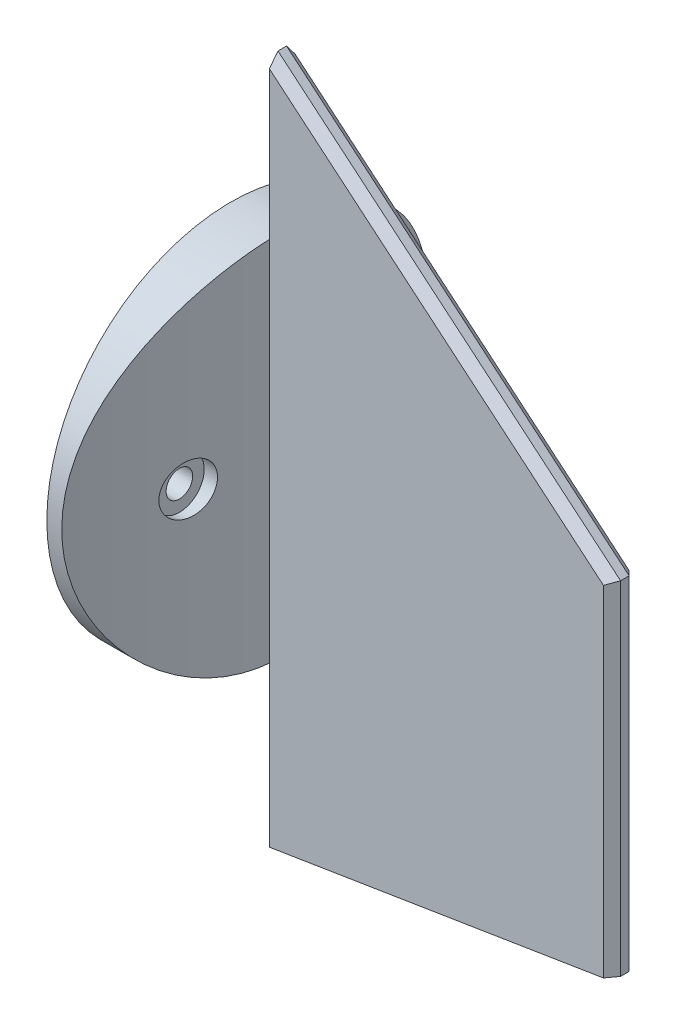
SolidWorks part; units mm, degrees
ref_plane "Front Plane" through (0, 0, 0) normal (0, 0, 1) x (1, 0, 0)
ref_plane "Top Plane" through (0, 0, 0) normal (0, 1, 0) x (1, 0, 0)
ref_plane "Right Plane" through (0, 0, 0) normal (1, 0, 0) x (0, 0, -1)
sketch "Sketch13" plane through (0, 0, 0) normal (1, 0, 0) x (0, 0, -1)
  line L0 (-2.6217, -2.2425) -> (-1.8172, -14.1833)
  line L1 (2.1766, -14.1326) -> (2.6778, -2.1753)
  arc A0 (2.6778, -2.1753) -> (-2.6217, -2.2425) centre (0, 0) ccw
  arc A1 (-1.8172, -14.1833) -> (2.1766, -14.1326) centre (0.1783, -14.0489) ccw
  circle A2 centre (0, 0) radius 16.3675
  dimension "D1" = 3.45
  dimension "D2" = 2
  dimension "D6" = 32.735
  dimension "D3" = 0.1783
  dimension "D4" = 2.1766
  dimension "D5" = 2.6778
extrude "Boss-Extrude11" add sketch "Sketch13" along normal mid plane 1.524
sketch "Sketch14" plane through (0.762, 0, 0) normal (1, 0, 0) x (0, 0, -1)
  circle A0 centre (0, 0) radius 16.3675
  circle A1 centre (0, 0) radius 16.3675 construction
extrude "Boss-Extrude12" add sketch "Sketch14" along normal mid plane 1.016
sketch "Sketch15" plane through (0, 0, 0) normal (0, 0, 1) x (1, 0, 0)
  line L0 (1.27, 18.3324) -> (1.27, -21.3321) construction
  line L1 (1.27, 0) -> (1.27, 25.4)
  line L2 (1.27, -16.3675) -> (1.27, 16.3675) construction
  line L3 (1.27, 0) -> (1.27, -25.4)
  line L4 (1.27, -25.4) -> (26.67, -21.3131)
  line L5 (26.67, -21.3131) -> (26.67, 4.0869)
  line L6 (26.67, 4.0869) -> (1.27, 25.4)
  dimension "D1" = 50
  dimension "D2" = 25.4
  dimension "D3" = 25.4
  dimension "D4" = 25.4
  dimension "D5" = 25.4
extrude "Boss-Extrude13" add sketch "Sketch15" along normal mid plane 1.905
fillet "Chamfer6" radius 0.762 4 edges at (13.97, 14.7434, -0.9525) (26.67, -8.6131, -0.9525) (26.67, -8.6131, 0.9525) (13.97, 14.7434, 0.9525) profile chamfer
sketch "Sketch20" plane through (-0.762, 0, 0) normal (-1, 0, 0) x (0, 0, 1)
  line L2 (1.8172, -14.1833) -> (2.6217, -2.2425)
  line L3 (-2.6778, -2.1753) -> (-2.1766, -14.1326)
  line L4 (1.8172, -14.1833) -> (2.6217, -2.2425)
  line L5 (-2.6778, -2.1753) -> (-2.1766, -14.1326)
  circle A1 centre (0, 0) radius 16.3675
  circle A2 centre (0, 0) radius 16.3675
  arc A4 (2.6217, -2.2425) -> (-2.6778, -2.1753) centre (0, 0) ccw
  arc A5 (-2.1766, -14.1326) -> (1.8172, -14.1833) centre (-0.1783, -14.0489) ccw
  arc A6 (2.6217, -2.2425) -> (-2.6778, -2.1753) centre (0, 0) ccw
  arc A7 (-2.1766, -14.1326) -> (1.8172, -14.1833) centre (-0.1783, -14.0489) ccw
  dimension "D1" = 0
  dimension "D2" = 0
sketch "Sketch26" plane through (0.254, 0, 0) normal (-1, 0, 0) x (0, 0, 1)
  line L2 (-2.6778, -2.1753) -> (-2.1766, -14.1326)
  line L3 (1.8172, -14.1833) -> (2.6217, -2.2425)
  line L4 (-2.6778, -2.1753) -> (-2.1766, -14.1326)
  line L5 (1.8172, -14.1833) -> (2.6217, -2.2425)
  arc A2 (2.6217, -2.2425) -> (-2.6778, -2.1753) centre (0, 0) ccw
  arc A3 (-2.1766, -14.1326) -> (1.8172, -14.1833) centre (-0.1783, -14.0489) ccw
  arc A4 (2.6217, -2.2425) -> (-2.6778, -2.1753) centre (0, 0) ccw
  arc A5 (-2.1766, -14.1326) -> (1.8172, -14.1833) centre (-0.1783, -14.0489) ccw
  dimension "D1" = 0
extrude "Boss-Extrude19" add sketch "Sketch26" along normal up to surface (1.016 mm away) up to face at (-0.762, 0, -16.3675)
sketch "Sketch27" plane through (1.27, 0, 0) normal (1, 0, 0) x (0, 0, -1)
  line L1 (0.9525, 16.3398) -> (0.9525, -16.3398)
  line L3 (0.9525, 16.3398) -> (0.9525, -16.3398)
  line L5 (-0.9525, -16.3398) -> (-0.9525, 16.3398)
  line L6 (-0.9525, -16.3398) -> (-0.9525, 16.3398)
  arc A1 (0.9525, -16.3398) -> (0.9525, 16.3398) centre (0, 0) ccw
  arc A2 (0.9525, -16.3398) -> (0.9525, 16.3398) centre (0, 0) ccw
  arc A3 (-0.9525, 16.3398) -> (-0.9525, -16.3398) centre (0, 0) ccw
  arc A4 (-0.9525, 16.3398) -> (-0.9525, -16.3398) centre (0, 0) ccw
  dimension "D1" = 0
  dimension "D2" = 0
extrude "Boss-Extrude20" add sketch "Sketch27" along normal blind 1.524
sketch "Sketch28" plane through (2.794, 0, 0) normal (1, 0, 0) x (0, 0, -1)
  line L0 (-23.2899, 0) -> (37.7845, 0) construction
  line L1 (-16.3675, 18.2766) -> (-16.3675, 10.7478) construction
  line L2 (0, 0) -> (0, -28.4596) construction
  circle A0 centre (-7.6248, 0) radius 2.2098
  arc A1 (-0.9525, 16.3398) -> (-0.9525, -16.3398) centre (0, 0) ccw construction
  circle A2 centre (7.6248, 0) radius 2.2098
  dimension "D1" = 4.4196
  dimension "D2" = 8.7427
extrude "Cut-Extrude9" cut sketch "Sketch28" against normal blind 1.524
sketch "Sketch29" plane through (1.27, 0, 0) normal (1, 0, 0) x (0, 0, -1)
  circle A0 centre (-7.6248, 0) radius 1.1811
  circle A1 centre (7.6248, 0) radius 1.1811
  dimension "D1" = 2.3622
  dimension "D2" = 2.3622
extrude "Cut-Extrude10" cut sketch "Sketch29" against normal blind 14.224
sketch "Sketch31" plane through (2.794, 0, 0) normal (1, 0, 0) x (0, 0, -1)
  line L0 (0.9525, 16.3398) -> (0.9525, -16.3398) construction
  line L1 (-0.9525, -16.3398) -> (-0.9525, 16.3398) construction
  line L2 (0.9525, 16.3398) -> (0.9525, -16.3398)
  line L3 (-0.9525, -16.3398) -> (-0.9525, 16.3398)
  circle A0 centre (7.6248, 0) radius 2.2098 construction
  circle A1 centre (-7.6248, 0) radius 2.2098
  circle A2 centre (-7.6248, 0) radius 2.2098
  circle A3 centre (7.6248, 0) radius 2.2098
  arc A4 (0.9525, -16.3398) -> (0.9525, 16.3398) centre (0, 0) ccw construction
  arc A5 (-0.9525, 16.3398) -> (-0.9525, -16.3398) centre (0, 0) ccw construction
  arc A6 (0.9525, -16.3398) -> (0.9525, 16.3398) centre (0, 0) ccw
  arc A7 (-0.9525, 16.3398) -> (-0.9525, -16.3398) centre (0, 0) ccw
  dimension "D1" = 0
sketch "Sketch32" plane through (-0.762, 0, 0) normal (-1, 0, 0) x (0, 0, 1)
  circle A0 centre (-7.6248, 0) radius 1.1811 construction
  circle A1 centre (-7.6248, 0) radius 1.1811
  circle A2 centre (7.6248, 0) radius 1.1811 construction
  circle A3 centre (7.6248, 0) radius 1.1811
  circle A5 centre (0, 0) radius 16.3675
  circle A6 centre (0, 0) radius 16.3675
  dimension "D1" = 0
sketch "Sketch35" plane through (2.794, 0, 0) normal (1, 0, 0) x (0, 0, -1)
  circle A0 centre (0, 0) radius 16.3675
  circle A1 centre (0, 0) radius 32.2294
extrude "Cut-Extrude15" cut sketch "Sketch35" along normal blind 52.832 contours A0
sketch "Sketch36" plane through (2.794, 0, 0) normal (1, 0, 0) x (0, 0, -1)
  circle A0 centre (0, 0) radius 29.1724
  circle A1 centre (0, 0) radius 16.3675
extrude "Cut-Extrude16" cut sketch "Sketch36" against normal blind 52.832 and the other way blind 52.832
sketch "Sketch33" plane through (0, 0, 0) normal (0, 1, 0) x (1, 0, 0)
  line L0 (-3.8217, 0) -> (38.6284, 0) construction
  line L2 (2.794, -16.3675) -> (2.794, 16.3675) construction
  line L3 (2.794, 16.3675) -> (-0.762, 16.3675) construction
  line L4 (-0.4519, 16.3675) -> (-0.762, 16.3675)
  line L5 (-0.4519, 16.3675) -> (-0.4519, -16.3675)
  line L6 (-0.4519, -16.3675) -> (-0.762, -16.3675)
  line L7 (-0.762, 16.3675) -> (-0.762, -16.3675)
  line L9 (-0.4519, 16.3675) -> (2.794, 16.3675)
  line L10 (-0.4519, 16.3675) -> (-0.4519, -16.3675)
  line L11 (-0.4519, -16.3675) -> (2.794, -16.3675)
  line L12 (2.794, 16.3675) -> (2.794, -16.3675)
  circle A0 centre (-40.0958, 0) radius 42.8898
  dimension "D1" = 85.7797
extrude "Cut-Extrude17" cut sketch "Sketch33" against normal blind 52.832 and the other way blind 52.832 contours A0 L11 L12 | A0 L12 L9 region at (1.8269, 0, -12.3072) region at (1.8269, 0, 12.3072)
ref_plane "Plane6" through (0, 0, 0) normal (0, 0, -1) x (-1, 0, 0)
sketch "Sketch38" plane through (0, 0, 0) normal (0, 0, -1) x (-1, 0, 0)
  line L0 (-2.794, 0) -> (-2.794, 30.48)
  line L1 (-2.794, 16.3675) -> (-2.794, -16.3675) construction
  line L2 (-2.794, 30.48) -> (-2.794, 0)
  line L3 (-2.794, 0) -> (-2.794, -30.48)
  line L4 (-2.794, -30.48) -> (-33.274, -25.5758)
  line L5 (-33.274, -25.5758) -> (-33.274, 4.9042)
  line L6 (-33.274, 4.9042) -> (-2.794, 30.48)
  line L7 (-2.794, 30.48) -> (-38.6624, 30.48) construction
  dimension "D1" = 30.48
  dimension "D2" = 30.48
  dimension "D3" = 40
  dimension "D4" = 30.48
  dimension "D5" = 30.48
extrude "Boss-Extrude21" add sketch "Sketch38" along normal mid plane 2.286 separate body contours L6 L5 L4 L3 L0 region at (16.3407, -4.5937, 0)
fillet "Chamfer7" radius 0.762 4 edges at (33.274, -10.3358, 1.143) (33.274, -10.3358, -1.143) (18.034, 17.6921, -1.143) (18.034, 17.6921, 1.143) profile chamfer
sketch "Sketch39" plane through (-0.762, 0, 0) normal (-1, 0, 0) x (0, 0, 1)
  circle A1 centre (0, 0) radius 16.3675
  circle A2 centre (0, 0) radius 16.3675
  dimension "D1" = 0
sketch "Sketch41" plane through (-0.762, 0, 0) normal (-1, 0, 0) x (0, 0, 1)
  circle A0 centre (0, 0) radius 2.921
  circle A1 centre (0, 0) radius 16.3675
  circle A2 centre (0, 0) radius 16.3675
  dimension "D2" = 5.842
  dimension "D1" = 0
extrude "Cut-Extrude19" cut sketch "Sketch41" against normal blind 1.524 contours A0 region at (-0.762, 0, 0)
sketch "Sketch42" plane through (-0.762, 0, 0) normal (-1, 0, 0) x (0, 0, 1)
  circle A0 centre (0, 0) radius 4.064
  dimension "D1" = 8.128
extrude "Cut-Extrude20" cut sketch "Sketch42" against normal mid plane 1.524
sketch "Sketch43" plane through (0.762, 0, 0) normal (-1, 0, 0) x (0, 0, 1)
  circle A1 centre (0, 0) radius 2.921
  circle A2 centre (0, 0) radius 2.921
  dimension "D1" = 0
extrude "Cut-Extrude21" cut sketch "Sketch43" against normal mid plane 1.016
sketch "Sketch44" plane through (0, 0, 0) normal (-1, 0, 0) x (0, 0, 1)
  circle A3 centre (0, 0) radius 5.4102
  point P1 (-13.1272, -0.9257)
  point P7 (-25.1158, -0.1986)
  dimension "D3" = 10.8204
extrude "Cut-Extrude24" cut sketch "Sketch44" against normal blind 0.9398 and the other way blind 0.9398
sketch "Sketch46" plane through (1.27, 0, 0) normal (-1, 0, 0) x (0, 0, 1)
  circle A1 centre (0, 0) radius 2.921
  circle A2 centre (0, 0) radius 2.921
  dimension "D1" = 0
extrude "Cut-Extrude25" cut sketch "Sketch46" against normal blind 0.508
sketch "Sketch47" plane through (-0.762, 0, 0) normal (-1, 0, 0) x (0, 0, 1)
  circle A0 centre (7.6248, 0) radius 1.1811 construction
  circle A1 centre (0, 0) radius 16.3675
  circle A2 centre (0, 0) radius 16.3675
  circle A3 centre (-7.6248, 0) radius 1.1811 construction
  circle A4 centre (0, 0) radius 5.4102 construction
  circle A5 centre (7.6248, 0) radius 1.1811
  circle A6 centre (-7.6248, 0) radius 1.1811
  circle A7 centre (0, 0) radius 5.4102
  dimension "D1" = 0
extrude "Boss-Extrude22" add sketch "Sketch47" along normal blind 1.016
sketch "Sketch48" plane through (0.9398, 0, 0) normal (-1, 0, 0) x (0, 0, 1)
  circle A0 centre (0, 0) radius 2.921 construction
  circle A1 centre (0, 0) radius 5.4102
  circle A2 centre (0, 0) radius 5.4102
  circle A3 centre (0, 0) radius 2.921
  dimension "D1" = 0
extrude "Boss-Extrude23" add sketch "Sketch48" along normal blind 1.524
sketch "Sketch49" plane through (1.778, 0, 0) normal (-1, 0, 0) x (0, 0, 1)
  circle A1 centre (0, 0) radius 2.921
  circle A2 centre (0, 0) radius 2.921
  dimension "D1" = 0
extrude "Boss-Extrude24" add sketch "Sketch49" along normal blind 0.762
sketch "Sketch17" plane through (0, 0, 0) normal (0, 1, 0) x (1, 0, 0)
  line L0 (2.7484, 0) -> (76.4286, 0) construction
  line L1 (1.27, -0.1905) -> (1.27, 0.1905) construction
  line L3 (-0.762, 16.3675) -> (1.27, 16.3675)
  line L4 (-0.762, 16.3675) -> (-0.762, -16.3675)
  line L5 (-0.4519, 0) -> (-0.762, 0) construction
  line L6 (-0.762, -16.3675) -> (1.27, -16.3675)
  line L7 (1.27, 16.3675) -> (1.27, -16.3675)
  circle A0 centre (-38.5818, 0) radius 39.8518
  point P3 (1.27, 0)
  dimension "D1" = 79.7036
extrude "Cut-Extrude5" [suppressed] cut sketch "Sketch17" against normal mid plane 50.8 contours A0 L4 L6 L7 | A0 L7 L3 L4
sketch "Sketch18" plane through (-0.762, 0, 0) normal (-1, 0, 0) x (0, 0, 1)
  line L0 (-2.803, -2.2222) -> (-2.3035, -14.138)
  line L1 (1.9439, -14.1919) -> (2.7457, -2.2927)
  line L2 (-2.6778, -2.1753) -> (-2.1766, -14.1326)
  line L3 (1.8172, -14.1833) -> (2.6217, -2.2425)
  line L4 (-2.6778, -2.1753) -> (-2.1766, -14.1326)
  line L5 (1.8172, -14.1833) -> (2.6217, -2.2425)
  arc A0 (2.7457, -2.2927) -> (-2.803, -2.2222) centre (0, 0) ccw
  arc A1 (-2.3035, -14.138) -> (1.9439, -14.1919) centre (-0.1783, -14.0489) ccw
  arc A2 (2.6217, -2.2425) -> (-2.6778, -2.1753) centre (0, 0) ccw
  arc A3 (-2.1766, -14.1326) -> (1.8172, -14.1833) centre (-0.1783, -14.0489) ccw
  arc A4 (2.6217, -2.2425) -> (-2.6778, -2.1753) centre (0, 0) ccw
  arc A5 (-2.1766, -14.1326) -> (1.8172, -14.1833) centre (-0.1783, -14.0489) ccw
  dimension "D1" = 0
  dimension "D2" = 0.127
extrude "Cut-Extrude6" [suppressed] cut sketch "Sketch18" against normal up to surface (1.016 mm away) up to face at (33.274, -10.3358, 0)
sketch "Sketch19" [suppressed] plane through (-0.762, 0, 0) normal (-1, 0, 0) x (0, 0, 1)
  line L2 (-12.563, 10.4913) -> (-12.563, -10.4913)
  line L3 (12.563, -10.4913) -> (12.563, 10.4913)
  line L4 (-12.563, 10.4913) -> (-12.563, -10.4913)
  line L5 (12.563, -10.4913) -> (12.563, 10.4913)
  line L6 (-2.803, -2.2222) -> (-2.3035, -14.138)
  line L7 (1.9439, -14.1919) -> (2.7457, -2.2927)
  line L8 (-2.803, -2.2222) -> (-2.3035, -14.138)
  line L9 (1.9439, -14.1919) -> (2.7457, -2.2927)
  arc A2 (-12.563, -10.4913) -> (12.563, -10.4913) centre (0, 0) ccw
  arc A3 (12.563, 10.4913) -> (-12.563, 10.4913) centre (0, 0) ccw
  arc A4 (-12.563, -10.4913) -> (12.563, -10.4913) centre (0, 0) ccw
  arc A5 (12.563, 10.4913) -> (-12.563, 10.4913) centre (0, 0) ccw
  arc A6 (2.7457, -2.2927) -> (-2.803, -2.2222) centre (0, 0) ccw
  arc A7 (-2.3035, -14.138) -> (1.9439, -14.1919) centre (-0.1783, -14.0489) ccw
  arc A8 (2.7457, -2.2927) -> (-2.803, -2.2222) centre (0, 0) ccw
  arc A9 (-2.3035, -14.138) -> (1.9439, -14.1919) centre (-0.1783, -14.0489) ccw
  dimension "D1" = 0
  dimension "D2" = 0
extrude "Boss-Extrude15" [suppressed] add sketch "Sketch19" along normal blind 2.54
